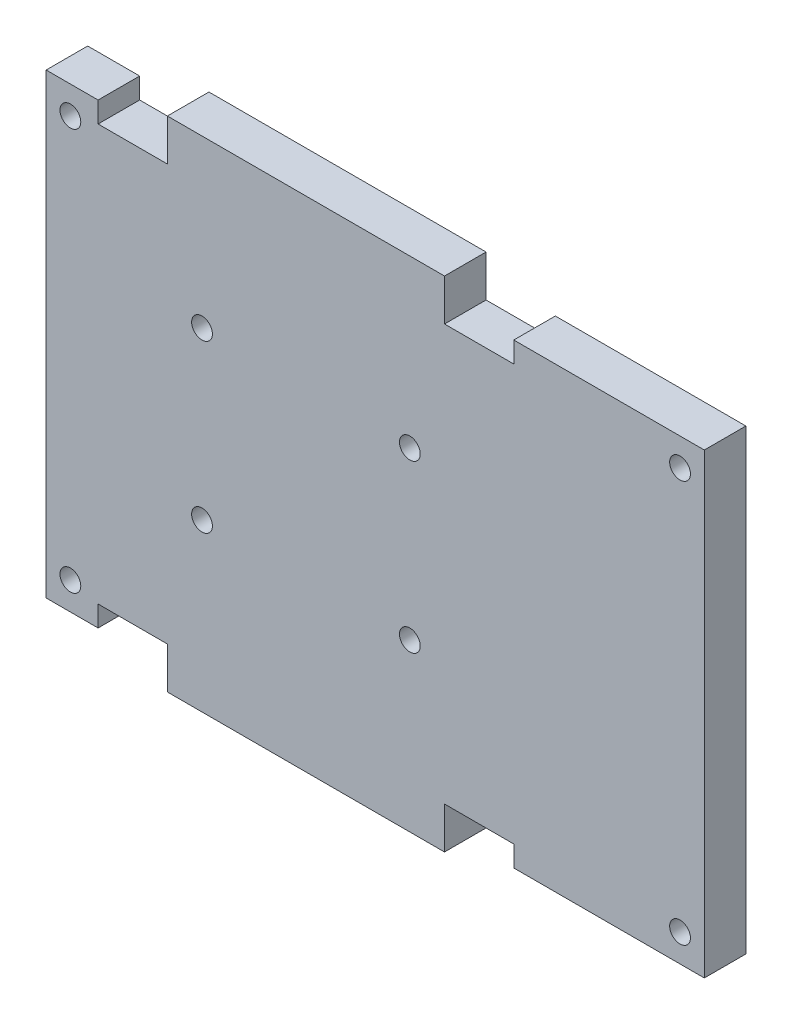
SolidWorks part; units mm, degrees
material "Pine"
ref_plane "Front Plane" through (0, 0, 0) normal (0, 0, 1) x (1, 0, 0)
ref_plane "Top Plane" through (0, 0, 0) normal (0, 1, 0) x (1, 0, 0)
ref_plane "Right Plane" through (0, 0, 0) normal (1, 0, 0) x (0, 0, -1)
sketch "Sketch1" plane through (0, 0, 0) normal (0, 0, 1) x (1, 0, 0)
  line L1 (-30, -36) -> (30, -36)
  line L2 (-30, -36) -> (-30, 36)
  line L3 (-30, 36) -> (30, 36)
  line L4 (30, -36) -> (30, 36)
  line L5 (-30, -36) -> (30, 36) construction
  line L6 (-30, 36) -> (30, -36) construction
  point P0 (0, 0)
  dimension "D1" = 72
  dimension "D2" = 60
extrude "Boss-Extrude1" add sketch "Sketch1" along normal blind 6
sketch "Sketch2" plane through (0, 0, 6) normal (0, 0, 1) x (1, 0, 0)
  line L0 (0, 0) -> (-30, 0) construction
  line L1 (-30, 36) -> (-20, 36)
  line L2 (-30, 36) -> (-30, 30)
  line L3 (-30, 30) -> (-20, 30)
  line L4 (-20, 36) -> (-20, 30)
  line L5 (-30, 36) -> (-30, -36) construction
  line L6 (-30, 0) -> (0, 0) construction
  line L7 (0, 0) -> (0, 36) construction
  line L8 (30, 36) -> (-30, 36) construction
  line L9 (-30, -30) -> (-20, -30)
  line L10 (-20, -36) -> (-20, -30)
  line L11 (-30, -36) -> (-20, -36)
  line L12 (-30, -36) -> (-30, -30)
  line L13 (30, -36) -> (30, -30)
  line L14 (30, -36) -> (20, -36)
  line L15 (20, -36) -> (20, -30)
  line L16 (30, -30) -> (20, -30)
  line L17 (30, 30) -> (20, 30)
  line L18 (20, 36) -> (20, 30)
  line L19 (30, 36) -> (20, 36)
  line L20 (30, 36) -> (30, 30)
  dimension "D1" = 6
  dimension "D2" = 10
extrude "Cut-Extrude1" cut sketch "Sketch2" against normal through all both and the other way through all
sketch "Sketch3" plane through (0, 0, 6) normal (0, 0, 1) x (1, 0, 0)
  line L1 (-15, -12) -> (15, -12) construction
  line L2 (-15, -12) -> (-15, 12) construction
  line L3 (-15, 12) -> (15, 12) construction
  line L4 (15, -12) -> (15, 12) construction
  line L5 (-15, -12) -> (15, 12) construction
  line L6 (-15, 12) -> (15, -12) construction
  circle A0 centre (-15, 12) radius 1.5
  circle A1 centre (-15, -12) radius 1.5
  circle A2 centre (15, -12) radius 1.5
  circle A3 centre (15, 12) radius 1.5
  point P0 (0, 0)
  dimension "D3" = 3
  dimension "D1" = 30
  dimension "D2" = 24
extrude "Cut-Extrude2" cut sketch "Sketch3" against normal through all both
sketch "Sketch6" plane through (30, 0, 0) normal (1, 0, 0) x (0, 0, -1)
  line L0 (-6, 30) -> (-6, 36) construction
  line L1 (-6, 33) -> (0, 33)
  line L2 (-6, 33) -> (-6, -33)
  line L3 (-6, -33) -> (0, -33)
  line L4 (0, 33) -> (0, -33)
  line L5 (0, -30) -> (0, -36) construction
  dimension "D1" = 66
extrude "Boss-Extrude2" add sketch "Sketch6" along normal blind 27.5
sketch "Sketch7" plane through (-30, 0, 0) normal (-1, 0, 0) x (0, 0, 1)
  line L0 (0, 30) -> (0, 36) construction
  line L1 (0, 33) -> (6, 33)
  line L2 (0, 33) -> (0, -33)
  line L3 (0, -33) -> (6, -33)
  line L4 (6, 33) -> (6, -33)
  line L5 (6, -30) -> (6, -36) construction
  point P8 (0, 0)
  dimension "D1" = 66
extrude "Boss-Extrude3" add sketch "Sketch7" along normal blind 7.5
sketch "Sketch8" plane through (0, 0, 6) normal (0, 0, 1) x (1, 0, 0)
  line L0 (57.5, -33) -> (30, -33) construction
  line L1 (57.5, 33) -> (57.5, -33) construction
  line L2 (57.5, 33) -> (30, 33) construction
  line L3 (-37.5, -33) -> (-37.5, 33) construction
  circle A0 centre (54, -29) radius 1.5
  circle A1 centre (54, 29) radius 1.5
  circle A2 centre (-34, 29) radius 1.5
  circle A3 centre (-34, -29) radius 1.5
  point P8 (0, 0)
  point P9 (0, 0)
  point P10 (0, 0)
  point P11 (0, 0)
  point P16 (54, 28.9839)
  dimension "D1" = 4
  dimension "D3" = 3
  dimension "D5" = 3.5
  dimension "D2" = 3.5
  dimension "D4" = 4
extrude "Cut-Extrude3" cut sketch "Sketch8" against normal through all
